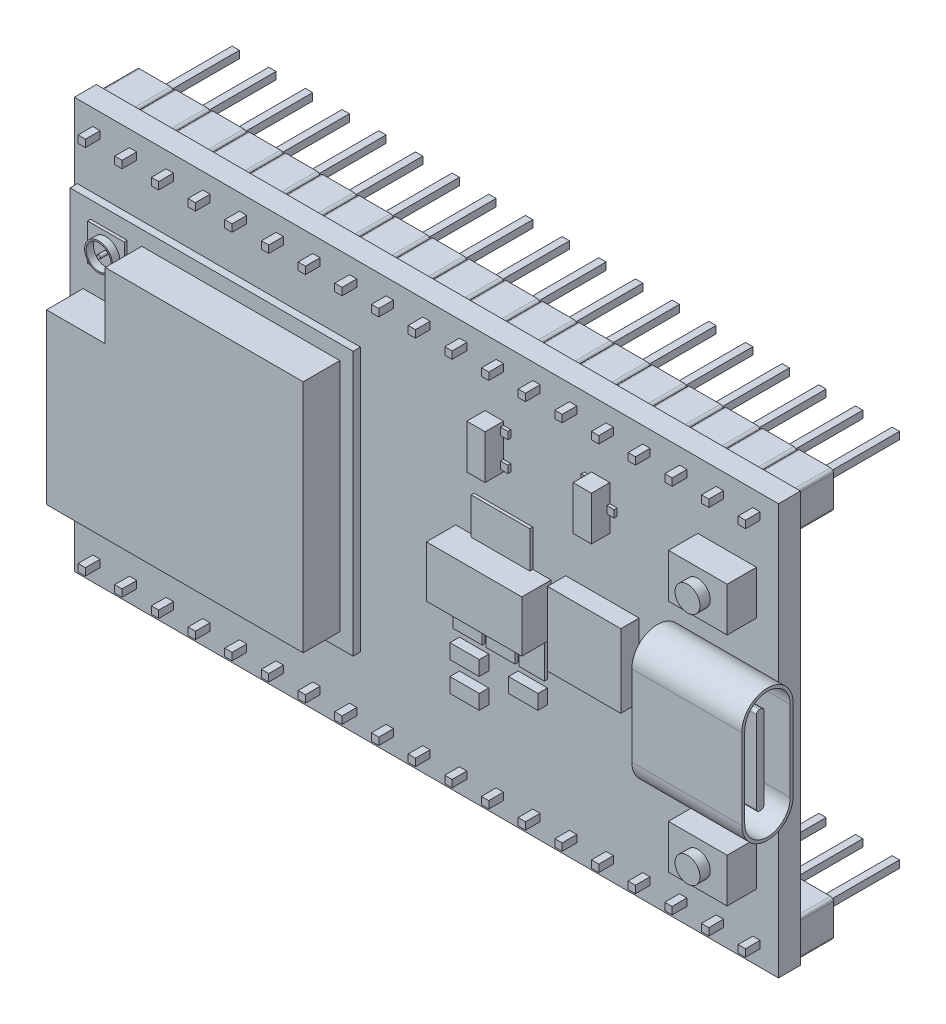
SolidWorks part; units mm, degrees
ref_plane "Front Plane" through (0, 0, 0) normal (0, 0, 1) x (1, 0, 0)
ref_plane "Top Plane" through (0, 0, 0) normal (0, 1, 0) x (1, 0, 0)
ref_plane "Right Plane" through (0, 0, 0) normal (1, 0, 0) x (0, 0, -1)
sketch "Sketch1" plane through (0, 0, 0) normal (0, 0, 1) x (1, 0, 0)
  line L1 (-24, -14) -> (24, -14)
  line L2 (-24, -14) -> (-24, 14)
  line L3 (-24, 14) -> (24, 14)
  line L4 (24, -14) -> (24, 14)
  dimension "D1" = 48
  dimension "D2" = 24
  dimension "D3" = 28
  dimension "D4" = 14
extrude "Boss-Extrude1" add sketch "Sketch1" along normal blind 1.5
sketch "Sketch2" plane through (0, 0, 0) normal (0, 0, -1) x (-1, 0, 0)
  line L1 (-23.55, -13.9) -> (-21.45, -13.9)
  line L2 (-23.75, -13.7) -> (-23.75, -11.6)
  line L3 (-23.55, -11.4) -> (-21.45, -11.4)
  line L6 (-21.05, -13.9) -> (-18.95, -13.9)
  line L8 (-21.05, -11.4) -> (-18.95, -11.4)
  line L10 (-18.55, -13.9) -> (-16.45, -13.9)
  line L12 (-18.55, -11.4) -> (-16.45, -11.4)
  line L14 (-16.05, -13.9) -> (-13.95, -13.9)
  line L16 (-16.05, -11.4) -> (-13.95, -11.4)
  line L18 (-13.55, -13.9) -> (-11.45, -13.9)
  line L20 (-13.55, -11.4) -> (-11.45, -11.4)
  line L22 (-11.05, -13.9) -> (-8.95, -13.9)
  line L24 (-11.05, -11.4) -> (-8.95, -11.4)
  line L26 (-8.55, -13.9) -> (-6.45, -13.9)
  line L28 (-8.55, -11.4) -> (-6.45, -11.4)
  line L30 (-6.05, -13.9) -> (-3.95, -13.9)
  line L32 (-6.05, -11.4) -> (-3.95, -11.4)
  line L34 (-3.55, -13.9) -> (-1.45, -13.9)
  line L36 (-3.55, -11.4) -> (-1.45, -11.4)
  line L38 (-1.05, -13.9) -> (1.05, -13.9)
  line L40 (-1.05, -11.4) -> (1.05, -11.4)
  line L42 (1.45, -13.9) -> (3.55, -13.9)
  line L44 (1.45, -11.4) -> (3.55, -11.4)
  line L46 (3.95, -13.9) -> (6.05, -13.9)
  line L48 (3.95, -11.4) -> (6.05, -11.4)
  line L50 (6.45, -13.9) -> (8.55, -13.9)
  line L52 (6.45, -11.4) -> (8.55, -11.4)
  line L54 (8.95, -13.9) -> (11.05, -13.9)
  line L56 (8.95, -11.4) -> (11.05, -11.4)
  line L58 (11.45, -13.9) -> (13.55, -13.9)
  line L60 (11.45, -11.4) -> (13.55, -11.4)
  line L62 (13.95, -13.9) -> (16.05, -13.9)
  line L64 (13.95, -11.4) -> (16.05, -11.4)
  line L66 (16.45, -13.9) -> (18.55, -13.9)
  line L68 (16.45, -11.4) -> (18.55, -11.4)
  line L70 (18.95, -13.9) -> (21.05, -13.9)
  line L72 (18.95, -11.4) -> (21.05, -11.4)
  line L74 (21.45, -13.9) -> (23.55, -13.9)
  line L75 (23.75, -13.7) -> (23.75, -11.6)
  line L76 (21.45, -11.4) -> (23.55, -11.4)
  line L78 (-24, -14) -> (-24, 14) construction
  line L79 (-1000, 0) -> (49000, 0) construction
  line L80 (21.45, 11.4) -> (23.55, 11.4)
  line L81 (23.75, 13.7) -> (23.75, 11.6)
  line L82 (21.45, 13.9) -> (23.55, 13.9)
  line L84 (18.95, 11.4) -> (21.05, 11.4)
  line L86 (18.95, 13.9) -> (21.05, 13.9)
  line L88 (16.45, 11.4) -> (18.55, 11.4)
  line L90 (16.45, 13.9) -> (18.55, 13.9)
  line L92 (13.95, 11.4) -> (16.05, 11.4)
  line L94 (13.95, 13.9) -> (16.05, 13.9)
  line L96 (11.45, 11.4) -> (13.55, 11.4)
  line L98 (11.45, 13.9) -> (13.55, 13.9)
  line L100 (8.95, 11.4) -> (11.05, 11.4)
  line L102 (8.95, 13.9) -> (11.05, 13.9)
  line L104 (6.45, 11.4) -> (8.55, 11.4)
  line L106 (6.45, 13.9) -> (8.55, 13.9)
  line L108 (3.95, 11.4) -> (6.05, 11.4)
  line L110 (3.95, 13.9) -> (6.05, 13.9)
  line L112 (1.45, 11.4) -> (3.55, 11.4)
  line L114 (1.45, 13.9) -> (3.55, 13.9)
  line L116 (-1.05, 11.4) -> (1.05, 11.4)
  line L118 (-1.05, 13.9) -> (1.05, 13.9)
  line L120 (-3.55, 11.4) -> (-1.45, 11.4)
  line L122 (-3.55, 13.9) -> (-1.45, 13.9)
  line L124 (-6.05, 11.4) -> (-3.95, 11.4)
  line L126 (-6.05, 13.9) -> (-3.95, 13.9)
  line L128 (-8.55, 11.4) -> (-6.45, 11.4)
  line L130 (-8.55, 13.9) -> (-6.45, 13.9)
  line L132 (-11.05, 11.4) -> (-8.95, 11.4)
  line L134 (-11.05, 13.9) -> (-8.95, 13.9)
  line L136 (-13.55, 11.4) -> (-11.45, 11.4)
  line L138 (-13.55, 13.9) -> (-11.45, 13.9)
  line L140 (-16.05, 11.4) -> (-13.95, 11.4)
  line L142 (-16.05, 13.9) -> (-13.95, 13.9)
  line L144 (-18.55, 11.4) -> (-16.45, 11.4)
  line L146 (-18.55, 13.9) -> (-16.45, 13.9)
  line L148 (-21.05, 11.4) -> (-18.95, 11.4)
  line L150 (-21.05, 13.9) -> (-18.95, 13.9)
  line L153 (-23.55, 11.4) -> (-21.45, 11.4)
  line L154 (-23.75, 13.7) -> (-23.75, 11.6)
  line L155 (-23.55, 13.9) -> (-21.45, 13.9)
  line L157 (21.25, -13.7) -> (21.25, -11.6) [skipped]
  line L158 (18.75, -13.7) -> (18.75, -11.6) [skipped]
  line L160 (16.25, -13.7) -> (16.25, -11.6) [skipped]
  line L163 (13.75, -13.7) -> (13.75, -11.6) [skipped]
  line L165 (11.25, -13.7) -> (11.25, -11.6) [skipped]
  line L166 (8.75, -13.7) -> (8.75, -11.6) [skipped]
  line L169 (6.25, -13.7) -> (6.25, -11.6) [skipped]
  line L171 (3.75, -13.7) -> (3.75, -11.6) [skipped]
  line L173 (1.25, -13.7) -> (1.25, -11.6) [skipped]
  line L175 (-1.25, -13.7) -> (-1.25, -11.6) [skipped]
  line L177 (-3.75, -13.7) -> (-3.75, -11.6) [skipped]
  line L179 (-6.25, -13.7) -> (-6.25, -11.6) [skipped]
  line L181 (-8.75, -13.7) -> (-8.75, -11.6) [skipped]
  line L183 (-11.25, -13.7) -> (-11.25, -11.6) [skipped]
  line L185 (-13.75, -13.7) -> (-13.75, -11.6) [skipped]
  line L187 (-16.25, -13.7) -> (-16.25, -11.6) [skipped]
  line L189 (-18.75, -13.7) -> (-18.75, -11.6) [skipped]
  line L190 (-21.25, -13.7) -> (-21.25, -11.6) [skipped]
  arc A0 (-23.55, -13.9) -> (-23.75, -13.7) centre (-23.55, -13.7) cw
  arc A1 (-21.45, -13.9) -> (-21.25, -13.7) centre (-21.45, -13.7) ccw
  arc A2 (-21.45, -11.4) -> (-21.25, -11.6) centre (-21.45, -11.6) cw
  arc A3 (-23.75, -11.6) -> (-23.55, -11.4) centre (-23.55, -11.6) cw
  arc A4 (-21.25, -11.6) -> (-21.05, -11.4) centre (-21.05, -11.6) cw
  arc A5 (-21.05, -13.9) -> (-21.25, -13.7) centre (-21.05, -13.7) cw
  arc A6 (-18.95, -13.9) -> (-18.75, -13.7) centre (-18.95, -13.7) ccw
  arc A7 (-18.95, -11.4) -> (-18.75, -11.6) centre (-18.95, -11.6) cw
  arc A8 (-18.75, -11.6) -> (-18.55, -11.4) centre (-18.55, -11.6) cw
  arc A9 (-18.55, -13.9) -> (-18.75, -13.7) centre (-18.55, -13.7) cw
  arc A10 (-16.45, -13.9) -> (-16.25, -13.7) centre (-16.45, -13.7) ccw
  arc A11 (-16.45, -11.4) -> (-16.25, -11.6) centre (-16.45, -11.6) cw
  arc A12 (-16.25, -11.6) -> (-16.05, -11.4) centre (-16.05, -11.6) cw
  arc A13 (-16.05, -13.9) -> (-16.25, -13.7) centre (-16.05, -13.7) cw
  arc A14 (-13.95, -13.9) -> (-13.75, -13.7) centre (-13.95, -13.7) ccw
  arc A15 (-13.95, -11.4) -> (-13.75, -11.6) centre (-13.95, -11.6) cw
  arc A16 (-13.75, -11.6) -> (-13.55, -11.4) centre (-13.55, -11.6) cw
  arc A17 (-13.55, -13.9) -> (-13.75, -13.7) centre (-13.55, -13.7) cw
  arc A18 (-11.45, -13.9) -> (-11.25, -13.7) centre (-11.45, -13.7) ccw
  arc A19 (-11.45, -11.4) -> (-11.25, -11.6) centre (-11.45, -11.6) cw
  arc A20 (-11.25, -11.6) -> (-11.05, -11.4) centre (-11.05, -11.6) cw
  arc A21 (-11.05, -13.9) -> (-11.25, -13.7) centre (-11.05, -13.7) cw
  arc A22 (-8.95, -13.9) -> (-8.75, -13.7) centre (-8.95, -13.7) ccw
  arc A23 (-8.95, -11.4) -> (-8.75, -11.6) centre (-8.95, -11.6) cw
  arc A24 (-8.75, -11.6) -> (-8.55, -11.4) centre (-8.55, -11.6) cw
  arc A25 (-8.55, -13.9) -> (-8.75, -13.7) centre (-8.55, -13.7) cw
  arc A26 (-6.45, -13.9) -> (-6.25, -13.7) centre (-6.45, -13.7) ccw
  arc A27 (-6.45, -11.4) -> (-6.25, -11.6) centre (-6.45, -11.6) cw
  arc A28 (-6.25, -11.6) -> (-6.05, -11.4) centre (-6.05, -11.6) cw
  arc A29 (-6.05, -13.9) -> (-6.25, -13.7) centre (-6.05, -13.7) cw
  arc A30 (-3.95, -13.9) -> (-3.75, -13.7) centre (-3.95, -13.7) ccw
  arc A31 (-3.95, -11.4) -> (-3.75, -11.6) centre (-3.95, -11.6) cw
  arc A32 (-3.75, -11.6) -> (-3.55, -11.4) centre (-3.55, -11.6) cw
  arc A33 (-3.55, -13.9) -> (-3.75, -13.7) centre (-3.55, -13.7) cw
  arc A34 (-1.45, -13.9) -> (-1.25, -13.7) centre (-1.45, -13.7) ccw
  arc A35 (-1.45, -11.4) -> (-1.25, -11.6) centre (-1.45, -11.6) cw
  arc A36 (-1.25, -11.6) -> (-1.05, -11.4) centre (-1.05, -11.6) cw
  arc A37 (-1.05, -13.9) -> (-1.25, -13.7) centre (-1.05, -13.7) cw
  arc A38 (1.05, -13.9) -> (1.25, -13.7) centre (1.05, -13.7) ccw
  arc A39 (1.05, -11.4) -> (1.25, -11.6) centre (1.05, -11.6) cw
  arc A40 (1.25, -11.6) -> (1.45, -11.4) centre (1.45, -11.6) cw
  arc A41 (1.45, -13.9) -> (1.25, -13.7) centre (1.45, -13.7) cw
  arc A42 (3.55, -13.9) -> (3.75, -13.7) centre (3.55, -13.7) ccw
  arc A43 (3.55, -11.4) -> (3.75, -11.6) centre (3.55, -11.6) cw
  arc A44 (3.75, -11.6) -> (3.95, -11.4) centre (3.95, -11.6) cw
  arc A45 (3.95, -13.9) -> (3.75, -13.7) centre (3.95, -13.7) cw
  arc A46 (6.05, -13.9) -> (6.25, -13.7) centre (6.05, -13.7) ccw
  arc A47 (6.05, -11.4) -> (6.25, -11.6) centre (6.05, -11.6) cw
  arc A48 (6.25, -11.6) -> (6.45, -11.4) centre (6.45, -11.6) cw
  arc A49 (6.45, -13.9) -> (6.25, -13.7) centre (6.45, -13.7) cw
  arc A50 (8.55, -13.9) -> (8.75, -13.7) centre (8.55, -13.7) ccw
  arc A51 (8.55, -11.4) -> (8.75, -11.6) centre (8.55, -11.6) cw
  arc A52 (8.75, -11.6) -> (8.95, -11.4) centre (8.95, -11.6) cw
  arc A53 (8.95, -13.9) -> (8.75, -13.7) centre (8.95, -13.7) cw
  arc A54 (11.05, -13.9) -> (11.25, -13.7) centre (11.05, -13.7) ccw
  arc A55 (11.05, -11.4) -> (11.25, -11.6) centre (11.05, -11.6) cw
  arc A56 (11.25, -11.6) -> (11.45, -11.4) centre (11.45, -11.6) cw
  arc A57 (11.45, -13.9) -> (11.25, -13.7) centre (11.45, -13.7) cw
  arc A58 (13.55, -13.9) -> (13.75, -13.7) centre (13.55, -13.7) ccw
  arc A59 (13.55, -11.4) -> (13.75, -11.6) centre (13.55, -11.6) cw
  arc A60 (13.75, -11.6) -> (13.95, -11.4) centre (13.95, -11.6) cw
  arc A61 (13.95, -13.9) -> (13.75, -13.7) centre (13.95, -13.7) cw
  arc A62 (16.05, -13.9) -> (16.25, -13.7) centre (16.05, -13.7) ccw
  arc A63 (16.05, -11.4) -> (16.25, -11.6) centre (16.05, -11.6) cw
  arc A64 (16.25, -11.6) -> (16.45, -11.4) centre (16.45, -11.6) cw
  arc A65 (16.45, -13.9) -> (16.25, -13.7) centre (16.45, -13.7) cw
  arc A66 (18.55, -13.9) -> (18.75, -13.7) centre (18.55, -13.7) ccw
  arc A67 (18.55, -11.4) -> (18.75, -11.6) centre (18.55, -11.6) cw
  arc A68 (18.75, -11.6) -> (18.95, -11.4) centre (18.95, -11.6) cw
  arc A69 (18.95, -13.9) -> (18.75, -13.7) centre (18.95, -13.7) cw
  arc A70 (21.05, -13.9) -> (21.25, -13.7) centre (21.05, -13.7) ccw
  arc A71 (21.05, -11.4) -> (21.25, -11.6) centre (21.05, -11.6) cw
  arc A72 (21.25, -11.6) -> (21.45, -11.4) centre (21.45, -11.6) cw
  arc A73 (21.45, -13.9) -> (21.25, -13.7) centre (21.45, -13.7) cw
  arc A74 (23.55, -13.9) -> (23.75, -13.7) centre (23.55, -13.7) ccw
  arc A75 (23.55, -11.4) -> (23.75, -11.6) centre (23.55, -11.6) cw
  arc A76 (23.55, 11.4) -> (23.75, 11.6) centre (23.55, 11.6) ccw
  arc A77 (23.55, 13.9) -> (23.75, 13.7) centre (23.55, 13.7) cw
  arc A78 (21.45, 13.9) -> (21.25, 13.7) centre (21.45, 13.7) ccw
  arc A79 (21.25, 11.6) -> (21.45, 11.4) centre (21.45, 11.6) ccw
  arc A80 (21.05, 11.4) -> (21.25, 11.6) centre (21.05, 11.6) ccw
  arc A81 (21.05, 13.9) -> (21.25, 13.7) centre (21.05, 13.7) cw
  arc A82 (18.95, 13.9) -> (18.75, 13.7) centre (18.95, 13.7) ccw
  arc A83 (18.75, 11.6) -> (18.95, 11.4) centre (18.95, 11.6) ccw
  arc A84 (18.55, 11.4) -> (18.75, 11.6) centre (18.55, 11.6) ccw
  arc A85 (18.55, 13.9) -> (18.75, 13.7) centre (18.55, 13.7) cw
  arc A86 (16.45, 13.9) -> (16.25, 13.7) centre (16.45, 13.7) ccw
  arc A87 (16.25, 11.6) -> (16.45, 11.4) centre (16.45, 11.6) ccw
  arc A88 (16.05, 11.4) -> (16.25, 11.6) centre (16.05, 11.6) ccw
  arc A89 (16.05, 13.9) -> (16.25, 13.7) centre (16.05, 13.7) cw
  arc A90 (13.95, 13.9) -> (13.75, 13.7) centre (13.95, 13.7) ccw
  arc A91 (13.75, 11.6) -> (13.95, 11.4) centre (13.95, 11.6) ccw
  arc A92 (13.55, 11.4) -> (13.75, 11.6) centre (13.55, 11.6) ccw
  arc A93 (13.55, 13.9) -> (13.75, 13.7) centre (13.55, 13.7) cw
  arc A94 (11.45, 13.9) -> (11.25, 13.7) centre (11.45, 13.7) ccw
  arc A95 (11.25, 11.6) -> (11.45, 11.4) centre (11.45, 11.6) ccw
  arc A96 (11.05, 11.4) -> (11.25, 11.6) centre (11.05, 11.6) ccw
  arc A97 (11.05, 13.9) -> (11.25, 13.7) centre (11.05, 13.7) cw
  arc A98 (8.95, 13.9) -> (8.75, 13.7) centre (8.95, 13.7) ccw
  arc A99 (8.75, 11.6) -> (8.95, 11.4) centre (8.95, 11.6) ccw
  arc A100 (8.55, 11.4) -> (8.75, 11.6) centre (8.55, 11.6) ccw
  arc A101 (8.55, 13.9) -> (8.75, 13.7) centre (8.55, 13.7) cw
  arc A102 (6.45, 13.9) -> (6.25, 13.7) centre (6.45, 13.7) ccw
  arc A103 (6.25, 11.6) -> (6.45, 11.4) centre (6.45, 11.6) ccw
  arc A104 (6.05, 11.4) -> (6.25, 11.6) centre (6.05, 11.6) ccw
  arc A105 (6.05, 13.9) -> (6.25, 13.7) centre (6.05, 13.7) cw
  arc A106 (3.95, 13.9) -> (3.75, 13.7) centre (3.95, 13.7) ccw
  arc A107 (3.75, 11.6) -> (3.95, 11.4) centre (3.95, 11.6) ccw
  arc A108 (3.55, 11.4) -> (3.75, 11.6) centre (3.55, 11.6) ccw
  arc A109 (3.55, 13.9) -> (3.75, 13.7) centre (3.55, 13.7) cw
  arc A110 (1.45, 13.9) -> (1.25, 13.7) centre (1.45, 13.7) ccw
  arc A111 (1.25, 11.6) -> (1.45, 11.4) centre (1.45, 11.6) ccw
  arc A112 (1.05, 11.4) -> (1.25, 11.6) centre (1.05, 11.6) ccw
  arc A113 (1.05, 13.9) -> (1.25, 13.7) centre (1.05, 13.7) cw
  arc A114 (-1.05, 13.9) -> (-1.25, 13.7) centre (-1.05, 13.7) ccw
  arc A115 (-1.25, 11.6) -> (-1.05, 11.4) centre (-1.05, 11.6) ccw
  arc A116 (-1.45, 11.4) -> (-1.25, 11.6) centre (-1.45, 11.6) ccw
  arc A117 (-1.45, 13.9) -> (-1.25, 13.7) centre (-1.45, 13.7) cw
  arc A118 (-3.55, 13.9) -> (-3.75, 13.7) centre (-3.55, 13.7) ccw
  arc A119 (-3.75, 11.6) -> (-3.55, 11.4) centre (-3.55, 11.6) ccw
  arc A120 (-3.95, 11.4) -> (-3.75, 11.6) centre (-3.95, 11.6) ccw
  arc A121 (-3.95, 13.9) -> (-3.75, 13.7) centre (-3.95, 13.7) cw
  arc A122 (-6.05, 13.9) -> (-6.25, 13.7) centre (-6.05, 13.7) ccw
  arc A123 (-6.25, 11.6) -> (-6.05, 11.4) centre (-6.05, 11.6) ccw
  arc A124 (-6.45, 11.4) -> (-6.25, 11.6) centre (-6.45, 11.6) ccw
  arc A125 (-6.45, 13.9) -> (-6.25, 13.7) centre (-6.45, 13.7) cw
  arc A126 (-8.55, 13.9) -> (-8.75, 13.7) centre (-8.55, 13.7) ccw
  arc A127 (-8.75, 11.6) -> (-8.55, 11.4) centre (-8.55, 11.6) ccw
  arc A128 (-8.95, 11.4) -> (-8.75, 11.6) centre (-8.95, 11.6) ccw
  arc A129 (-8.95, 13.9) -> (-8.75, 13.7) centre (-8.95, 13.7) cw
  arc A130 (-11.05, 13.9) -> (-11.25, 13.7) centre (-11.05, 13.7) ccw
  arc A131 (-11.25, 11.6) -> (-11.05, 11.4) centre (-11.05, 11.6) ccw
  arc A132 (-11.45, 11.4) -> (-11.25, 11.6) centre (-11.45, 11.6) ccw
  arc A133 (-11.45, 13.9) -> (-11.25, 13.7) centre (-11.45, 13.7) cw
  arc A134 (-13.55, 13.9) -> (-13.75, 13.7) centre (-13.55, 13.7) ccw
  arc A135 (-13.75, 11.6) -> (-13.55, 11.4) centre (-13.55, 11.6) ccw
  arc A136 (-13.95, 11.4) -> (-13.75, 11.6) centre (-13.95, 11.6) ccw
  arc A137 (-13.95, 13.9) -> (-13.75, 13.7) centre (-13.95, 13.7) cw
  arc A138 (-16.05, 13.9) -> (-16.25, 13.7) centre (-16.05, 13.7) ccw
  arc A139 (-16.25, 11.6) -> (-16.05, 11.4) centre (-16.05, 11.6) ccw
  arc A140 (-16.45, 11.4) -> (-16.25, 11.6) centre (-16.45, 11.6) ccw
  arc A141 (-16.45, 13.9) -> (-16.25, 13.7) centre (-16.45, 13.7) cw
  arc A142 (-18.55, 13.9) -> (-18.75, 13.7) centre (-18.55, 13.7) ccw
  arc A143 (-18.75, 11.6) -> (-18.55, 11.4) centre (-18.55, 11.6) ccw
  arc A144 (-18.95, 11.4) -> (-18.75, 11.6) centre (-18.95, 11.6) ccw
  arc A145 (-18.95, 13.9) -> (-18.75, 13.7) centre (-18.95, 13.7) cw
  arc A146 (-21.05, 13.9) -> (-21.25, 13.7) centre (-21.05, 13.7) ccw
  arc A147 (-21.25, 11.6) -> (-21.05, 11.4) centre (-21.05, 11.6) ccw
  arc A148 (-23.75, 11.6) -> (-23.55, 11.4) centre (-23.55, 11.6) ccw
  arc A149 (-21.45, 11.4) -> (-21.25, 11.6) centre (-21.45, 11.6) ccw
  arc A150 (-21.45, 13.9) -> (-21.25, 13.7) centre (-21.45, 13.7) cw
  arc A151 (-23.55, 13.9) -> (-23.75, 13.7) centre (-23.55, 13.7) ccw
  point P6 (-23.75, -13.9)
  point P9 (-21.25, -13.9)
  point P14 (-23.75, -11.4)
  point P430 (-23.75, 11.4)
  point P431 (-21.25, 13.9)
  point P432 (-23.75, 13.9)
  dimension "D3" = 0.2
  dimension "D1" = 2.5
  dimension "D2" = 2.5
  dimension "D5" = 0.25
  dimension "D6" = 13.9
  dimension "D4" = 19
extrude "Boss-Extrude2" add sketch "Sketch2" along normal blind 2.5
sketch "Sketch3" plane through (0, 0, -2.5) normal (0, 0, -1) x (-1, 0, 0)
  line L0 (-23.75, -11.6) -> (-23.75, -13.7) construction
  line L1 (-22.75, -12.9) -> (-22.25, -12.9)
  line L2 (-22.75, -12.9) -> (-22.75, -12.4)
  line L3 (-22.75, -12.4) -> (-22.25, -12.4)
  line L4 (-22.25, -12.9) -> (-22.25, -12.4)
  line L5 (-23.55, -13.9) -> (-21.45, -13.9) construction
  line L6 (-20.25, -12.9) -> (-20.25, -12.4)
  line L7 (-20.25, -12.9) -> (-19.75, -12.9)
  line L8 (-19.75, -12.9) -> (-19.75, -12.4)
  line L9 (-20.25, -12.4) -> (-19.75, -12.4)
  line L10 (-17.75, -12.9) -> (-17.75, -12.4)
  line L11 (-17.75, -12.9) -> (-17.25, -12.9)
  line L12 (-17.25, -12.9) -> (-17.25, -12.4)
  line L13 (-17.75, -12.4) -> (-17.25, -12.4)
  line L14 (-15.25, -12.9) -> (-15.25, -12.4)
  line L15 (-15.25, -12.9) -> (-14.75, -12.9)
  line L16 (-14.75, -12.9) -> (-14.75, -12.4)
  line L17 (-15.25, -12.4) -> (-14.75, -12.4)
  line L18 (-12.75, -12.9) -> (-12.75, -12.4)
  line L19 (-12.75, -12.9) -> (-12.25, -12.9)
  line L20 (-12.25, -12.9) -> (-12.25, -12.4)
  line L21 (-12.75, -12.4) -> (-12.25, -12.4)
  line L22 (-10.25, -12.9) -> (-10.25, -12.4)
  line L23 (-10.25, -12.9) -> (-9.75, -12.9)
  line L24 (-9.75, -12.9) -> (-9.75, -12.4)
  line L25 (-10.25, -12.4) -> (-9.75, -12.4)
  line L26 (-7.75, -12.9) -> (-7.75, -12.4)
  line L27 (-7.75, -12.9) -> (-7.25, -12.9)
  line L28 (-7.25, -12.9) -> (-7.25, -12.4)
  line L29 (-7.75, -12.4) -> (-7.25, -12.4)
  line L30 (-5.25, -12.9) -> (-5.25, -12.4)
  line L31 (-5.25, -12.9) -> (-4.75, -12.9)
  line L32 (-4.75, -12.9) -> (-4.75, -12.4)
  line L33 (-5.25, -12.4) -> (-4.75, -12.4)
  line L34 (-2.75, -12.9) -> (-2.75, -12.4)
  line L35 (-2.75, -12.9) -> (-2.25, -12.9)
  line L36 (-2.25, -12.9) -> (-2.25, -12.4)
  line L37 (-2.75, -12.4) -> (-2.25, -12.4)
  line L38 (-0.25, -12.9) -> (-0.25, -12.4)
  line L39 (-0.25, -12.9) -> (0.25, -12.9)
  line L40 (0.25, -12.9) -> (0.25, -12.4)
  line L41 (-0.25, -12.4) -> (0.25, -12.4)
  line L42 (2.25, -12.9) -> (2.25, -12.4)
  line L43 (2.25, -12.9) -> (2.75, -12.9)
  line L44 (2.75, -12.9) -> (2.75, -12.4)
  line L45 (2.25, -12.4) -> (2.75, -12.4)
  line L46 (4.75, -12.9) -> (4.75, -12.4)
  line L47 (4.75, -12.9) -> (5.25, -12.9)
  line L48 (5.25, -12.9) -> (5.25, -12.4)
  line L49 (4.75, -12.4) -> (5.25, -12.4)
  line L50 (7.25, -12.9) -> (7.25, -12.4)
  line L51 (7.25, -12.9) -> (7.75, -12.9)
  line L52 (7.75, -12.9) -> (7.75, -12.4)
  line L53 (7.25, -12.4) -> (7.75, -12.4)
  line L54 (9.75, -12.9) -> (9.75, -12.4)
  line L55 (9.75, -12.9) -> (10.25, -12.9)
  line L56 (10.25, -12.9) -> (10.25, -12.4)
  line L57 (9.75, -12.4) -> (10.25, -12.4)
  line L58 (12.25, -12.9) -> (12.25, -12.4)
  line L59 (12.25, -12.9) -> (12.75, -12.9)
  line L60 (12.75, -12.9) -> (12.75, -12.4)
  line L61 (12.25, -12.4) -> (12.75, -12.4)
  line L62 (14.75, -12.9) -> (14.75, -12.4)
  line L63 (14.75, -12.9) -> (15.25, -12.9)
  line L64 (15.25, -12.9) -> (15.25, -12.4)
  line L65 (14.75, -12.4) -> (15.25, -12.4)
  line L66 (17.25, -12.9) -> (17.25, -12.4)
  line L67 (17.25, -12.9) -> (17.75, -12.9)
  line L68 (17.75, -12.9) -> (17.75, -12.4)
  line L69 (17.25, -12.4) -> (17.75, -12.4)
  line L70 (19.75, -12.9) -> (19.75, -12.4)
  line L71 (19.75, -12.9) -> (20.25, -12.9)
  line L72 (20.25, -12.9) -> (20.25, -12.4)
  line L73 (19.75, -12.4) -> (20.25, -12.4)
  line L74 (22.25, -12.9) -> (22.25, -12.4)
  line L75 (22.25, -12.9) -> (22.75, -12.9)
  line L76 (22.75, -12.9) -> (22.75, -12.4)
  line L77 (22.25, -12.4) -> (22.75, -12.4)
  line L78 (-1000, 0) -> (49000, 0) construction
  line L79 (22.25, 12.4) -> (22.75, 12.4)
  line L80 (22.75, 12.9) -> (22.75, 12.4)
  line L81 (22.25, 12.9) -> (22.75, 12.9)
  line L82 (22.25, 12.9) -> (22.25, 12.4)
  line L83 (19.75, 12.4) -> (20.25, 12.4)
  line L84 (20.25, 12.9) -> (20.25, 12.4)
  line L85 (19.75, 12.9) -> (20.25, 12.9)
  line L86 (19.75, 12.9) -> (19.75, 12.4)
  line L87 (17.25, 12.4) -> (17.75, 12.4)
  line L88 (17.75, 12.9) -> (17.75, 12.4)
  line L89 (17.25, 12.9) -> (17.75, 12.9)
  line L90 (17.25, 12.9) -> (17.25, 12.4)
  line L91 (14.75, 12.4) -> (15.25, 12.4)
  line L92 (15.25, 12.9) -> (15.25, 12.4)
  line L93 (14.75, 12.9) -> (15.25, 12.9)
  line L94 (14.75, 12.9) -> (14.75, 12.4)
  line L95 (12.25, 12.4) -> (12.75, 12.4)
  line L96 (12.75, 12.9) -> (12.75, 12.4)
  line L97 (12.25, 12.9) -> (12.75, 12.9)
  line L98 (12.25, 12.9) -> (12.25, 12.4)
  line L99 (9.75, 12.4) -> (10.25, 12.4)
  line L100 (10.25, 12.9) -> (10.25, 12.4)
  line L101 (9.75, 12.9) -> (10.25, 12.9)
  line L102 (9.75, 12.9) -> (9.75, 12.4)
  line L103 (7.25, 12.4) -> (7.75, 12.4)
  line L104 (7.75, 12.9) -> (7.75, 12.4)
  line L105 (7.25, 12.9) -> (7.75, 12.9)
  line L106 (7.25, 12.9) -> (7.25, 12.4)
  line L107 (4.75, 12.4) -> (5.25, 12.4)
  line L108 (5.25, 12.9) -> (5.25, 12.4)
  line L109 (4.75, 12.9) -> (5.25, 12.9)
  line L110 (4.75, 12.9) -> (4.75, 12.4)
  line L111 (2.25, 12.4) -> (2.75, 12.4)
  line L112 (2.75, 12.9) -> (2.75, 12.4)
  line L113 (2.25, 12.9) -> (2.75, 12.9)
  line L114 (2.25, 12.9) -> (2.25, 12.4)
  line L115 (-0.25, 12.4) -> (0.25, 12.4)
  line L116 (0.25, 12.9) -> (0.25, 12.4)
  line L117 (-0.25, 12.9) -> (0.25, 12.9)
  line L118 (-0.25, 12.9) -> (-0.25, 12.4)
  line L119 (-2.75, 12.4) -> (-2.25, 12.4)
  line L120 (-2.25, 12.9) -> (-2.25, 12.4)
  line L121 (-2.75, 12.9) -> (-2.25, 12.9)
  line L122 (-2.75, 12.9) -> (-2.75, 12.4)
  line L123 (-5.25, 12.4) -> (-4.75, 12.4)
  line L124 (-4.75, 12.9) -> (-4.75, 12.4)
  line L125 (-5.25, 12.9) -> (-4.75, 12.9)
  line L126 (-5.25, 12.9) -> (-5.25, 12.4)
  line L127 (-7.75, 12.4) -> (-7.25, 12.4)
  line L128 (-7.25, 12.9) -> (-7.25, 12.4)
  line L129 (-7.75, 12.9) -> (-7.25, 12.9)
  line L130 (-7.75, 12.9) -> (-7.75, 12.4)
  line L131 (-10.25, 12.4) -> (-9.75, 12.4)
  line L132 (-9.75, 12.9) -> (-9.75, 12.4)
  line L133 (-10.25, 12.9) -> (-9.75, 12.9)
  line L134 (-10.25, 12.9) -> (-10.25, 12.4)
  line L135 (-12.75, 12.4) -> (-12.25, 12.4)
  line L136 (-12.25, 12.9) -> (-12.25, 12.4)
  line L137 (-12.75, 12.9) -> (-12.25, 12.9)
  line L138 (-12.75, 12.9) -> (-12.75, 12.4)
  line L139 (-15.25, 12.4) -> (-14.75, 12.4)
  line L140 (-14.75, 12.9) -> (-14.75, 12.4)
  line L141 (-15.25, 12.9) -> (-14.75, 12.9)
  line L142 (-15.25, 12.9) -> (-15.25, 12.4)
  line L143 (-17.75, 12.4) -> (-17.25, 12.4)
  line L144 (-17.25, 12.9) -> (-17.25, 12.4)
  line L145 (-17.75, 12.9) -> (-17.25, 12.9)
  line L146 (-17.75, 12.9) -> (-17.75, 12.4)
  line L147 (-20.25, 12.4) -> (-19.75, 12.4)
  line L148 (-19.75, 12.9) -> (-19.75, 12.4)
  line L149 (-20.25, 12.9) -> (-19.75, 12.9)
  line L150 (-20.25, 12.9) -> (-20.25, 12.4)
  line L151 (-22.25, 12.9) -> (-22.25, 12.4)
  line L152 (-22.75, 12.4) -> (-22.25, 12.4)
  line L153 (-22.75, 12.9) -> (-22.75, 12.4)
  line L154 (-22.75, 12.9) -> (-22.25, 12.9)
  point P6 (-23.75, -12.65)
  dimension "D1" = 0.5
  dimension "D2" = 0.5
  dimension "D3" = 1
  dimension "D4" = 1
  dimension "D5" = 19
extrude "Boss-Extrude3" add sketch "Sketch3" along normal blind 5.5 and the other way blind 5
sketch "Sketch4" plane through (24, 0, 0) normal (1, 0, 0) x (0, 0, -1)
  line L0 (-3.25, -2.75) -> (-3.25, 2.75) construction
  line L1 (-5, -2.75) -> (-5, 2.75)
  line L2 (-1.5, -2.75) -> (-1.5, 2.75)
  line L3 (-1.5, -14) -> (-1.5, 14) construction
  line L4 (-4.8, -2.75) -> (-4.8, 2.75)
  line L5 (-1.7, -2.75) -> (-1.7, 2.75)
  arc A0 (-5, -2.75) -> (-1.5, -2.75) centre (-3.25, -2.75) ccw
  arc A1 (-1.5, 2.75) -> (-5, 2.75) centre (-3.25, 2.75) ccw
  arc A2 (-1.7, 2.75) -> (-4.8, 2.75) centre (-3.25, 2.75) ccw
  arc A3 (-4.8, -2.75) -> (-1.7, -2.75) centre (-3.25, -2.75) ccw
  point P2 (-3.25, 0)
  dimension "D1" = 9
  dimension "D2" = 3.5
  dimension "D3" = 2.75
  dimension "D4" = 0.2
extrude "Boss-Extrude4" add sketch "Sketch4" along normal blind 7 from offset 6 offset against normal yes
sketch "Sketch5" plane through (18, 0, 0) normal (-1, 0, 0) x (0, 0, 1)
  line L2 (5, -2.75) -> (5, 2.75)
  line L3 (1.5, 2.75) -> (1.5, -2.75)
  line L4 (5, -2.75) -> (5, 2.75)
  line L5 (1.5, 2.75) -> (1.5, -2.75)
  arc A2 (1.5, -2.75) -> (5, -2.75) centre (3.25, -2.75) ccw
  arc A3 (5, 2.75) -> (1.5, 2.75) centre (3.25, 2.75) ccw
  arc A4 (1.5, -2.75) -> (5, -2.75) centre (3.25, -2.75) ccw
  arc A5 (5, 2.75) -> (1.5, 2.75) centre (3.25, 2.75) ccw
  dimension "D1" = 0
extrude "Boss-Extrude5" add sketch "Sketch5" along normal blind 0.5
sketch "Sketch6" plane through (18, 0, 0) normal (1, 0, 0) x (0, 0, -1)
  line L0 (-1.7, -2.75) -> (-1.7, 2.75) construction
  line L1 (-3.3, -3) -> (-3.2, -3)
  line L2 (-3.5, -2.8) -> (-3.5, 2.8)
  line L3 (-3.3, 3) -> (-3.2, 3)
  line L4 (-3, -2.8) -> (-3, 2.8)
  arc A0 (-3.3, -3) -> (-3.5, -2.8) centre (-3.3, -2.8) cw
  arc A1 (-3.2, -3) -> (-3, -2.8) centre (-3.2, -2.8) ccw
  arc A2 (-3.2, 3) -> (-3, 2.8) centre (-3.2, 2.8) cw
  arc A3 (-3.5, 2.8) -> (-3.3, 3) centre (-3.3, 2.8) cw
  point P6 (-3.5, -3)
  point P11 (-3, 3)
  point P14 (-3.5, 3)
  dimension "D3" = 0.2
  dimension "D1" = 6
  dimension "D2" = 0.5
  dimension "D4" = 3
  dimension "D5" = 1.3
extrude "Boss-Extrude6" add sketch "Sketch6" along normal blind 6.5
sketch "Sketch7" plane through (0, 0, 1.5) normal (0, 0, 1) x (1, 0, 0)
  line L0 (-24, 14) -> (-24, -14) construction
  line L1 (-23.8, -9) -> (-4.5, -9)
  line L2 (-23.8, -9) -> (-23.8, 9)
  line L3 (-23.8, 9) -> (-4.5, 9)
  line L4 (-4.5, -9) -> (-4.5, 9)
  dimension "D1" = 19.3
  dimension "D2" = 0.2
  dimension "D3" = 18
  dimension "D4" = 9
extrude "Boss-Extrude7" add sketch "Sketch7" along normal blind 0.5
sketch "Sketch8" plane through (0, 0, 2) normal (0, 0, 1) x (1, 0, 0)
  line L0 (-4.5, -9) -> (-4.5, 9) construction
  line L1 (-22.9, -8) -> (-5.4, -8)
  line L2 (-22.9, -8) -> (-22.9, 8)
  line L3 (-22.9, 8) -> (-5.4, 8)
  line L4 (-5.4, -8) -> (-5.4, 8)
  line L6 (-22.9, 8) -> (-18.9, 8)
  line L7 (-22.9, 8) -> (-22.9, 3.5)
  line L8 (-22.9, 3.5) -> (-18.9, 3.5)
  line L9 (-18.9, 8) -> (-18.9, 3.5)
  dimension "D1" = 17.5
  dimension "D2" = 16
  dimension "D3" = 8
  dimension "D4" = 0.9
  dimension "D5" = 4.5
  dimension "D6" = 4
extrude "Boss-Extrude8" add sketch "Sketch8" along normal blind 2.5 contours L3 L9 L8 L2 L1 L4 region at (-13.6863, -0.395, 2)
sketch "Sketch9" plane through (0, 0, 2) normal (0, 0, 1) x (1, 0, 0)
  line L0 (-18.9, 8) -> (-5.4, 8) construction
  line L1 (-22.4, 5.35) -> (-19.9, 5.35)
  line L2 (-22.4, 5.35) -> (-22.4, 7.85)
  line L3 (-22.4, 7.85) -> (-19.9, 7.85)
  line L4 (-19.9, 5.35) -> (-19.9, 7.85)
  line L5 (-22.9, -8) -> (-22.9, 3.5) construction
  dimension "D1" = 2.5
  dimension "D2" = 2.5
  dimension "D3" = 0.15
  dimension "D4" = 0.5
extrude "Boss-Extrude9" add sketch "Sketch9" along normal blind 0.2
sketch "Sketch10" plane through (0, 0, 2.2) normal (0, 0, 1) x (1, 0, 0)
  line L1 (-22.4, 7.85) -> (-22.4, 5.35) construction
  line L2 (-22.4, 5.35) -> (-19.9, 5.35) construction
  circle A0 centre (-21.15, 6.6) radius 0.95
  circle A1 centre (-21.15, 6.6) radius 0.85
  circle A2 centre (-21.15, 6.6) radius 0.125
  dimension "D1" = 1.9
  dimension "D5" = 0.25
  dimension "D2" = 1.25
  dimension "D3" = 1.25
  dimension "D4" = 0.1
extrude "Boss-Extrude10" add sketch "Sketch10" along normal blind 0.5 contours A0 A1 | A2 region at (-22.0731, 6.6, 2.2) region at (-21.15, 6.6, 2.2)
sketch "Sketch11" plane through (0, 0, 1.5) normal (0, 0, 1) x (1, 0, 0)
  line L0 (17.5, -2.75) -> (17.5, 2.75) construction
  line L1 (9.5, -2.5) -> (14.5, -2.5)
  line L2 (9.5, -2.5) -> (9.5, 2.5)
  line L3 (9.5, 2.5) -> (14.5, 2.5)
  line L4 (14.5, -2.5) -> (14.5, 2.5)
  line L6 (11.25, 6.5) -> (12.5, 6.5)
  line L7 (11.25, 6.5) -> (11.25, 9.5)
  line L8 (11.25, 9.5) -> (12.5, 9.5)
  line L9 (12.5, 6.5) -> (12.5, 9.5)
  line L10 (4, 6.5) -> (5.25, 6.5)
  line L11 (4, 6.5) -> (4, 9.5)
  line L12 (4, 9.5) -> (5.25, 9.5)
  line L13 (5.25, 6.5) -> (5.25, 9.5)
  dimension "D1" = 5
  dimension "D2" = 3
  dimension "D3" = 2.5
  dimension "D4" = 1.25
  dimension "D5" = 1.25
  dimension "D6" = 3
  dimension "D7" = 3
  dimension "D8" = 4
  dimension "D9" = 6
  dimension "D10" = 3
extrude "Boss-Extrude11" add sketch "Sketch11" along normal blind 1.25
sketch "Sketch12" plane through (0, 0, 1.5) normal (0, 0, 1) x (1, 0, 0)
  line L0 (9.5, 2.5) -> (9.5, -2.5) construction
  line L1 (2, -1.75) -> (8.5, -1.75)
  line L2 (2, -1.75) -> (2, 1.75)
  line L3 (2, 1.75) -> (8.5, 1.75)
  line L4 (8.5, -1.75) -> (8.5, 1.75)
  point P7 (9.5, 0)
  dimension "D1" = 6.5
  dimension "D2" = 3.5
  dimension "D3" = 1.75
  dimension "D4" = 1
extrude "Boss-Extrude12" add sketch "Sketch12" along normal blind 2
sketch "Sketch13" plane through (0, 0, 1.5) normal (0, 0, 1) x (1, 0, 0)
  line L0 (4, 9.5) -> (4, 6.5) construction
  line L1 (4, 7.75) -> (3.5, 7.75)
  line L2 (4, 7.75) -> (4, 8.25)
  line L3 (4, 8.25) -> (3.5, 8.25)
  line L4 (3.5, 7.75) -> (3.5, 8.25)
  line L6 (4, 6.5) -> (5.25, 6.5) construction
  line L7 (5.25, 6.5) -> (5.25, 9.5) construction
  line L8 (5.25, 8.75) -> (5.75, 8.75)
  line L9 (5.25, 8.75) -> (5.25, 9.25)
  line L10 (5.25, 9.25) -> (5.75, 9.25)
  line L11 (5.75, 8.75) -> (5.75, 9.25)
  line L12 (5.25, 9.5) -> (4, 9.5) construction
  line L13 (5.25, 7.25) -> (5.75, 7.25)
  line L14 (5.25, 7.25) -> (5.25, 6.75)
  line L15 (5.25, 6.75) -> (5.75, 6.75)
  line L16 (5.75, 7.25) -> (5.75, 6.75)
  line L17 (4, 6.5) -> (5.25, 6.5) construction
  line L18 (8.25, -992.2125) -> (8.25, 49007.7875) construction
  line L19 (5.25, 6.5) -> (11.25, 6.5)
  line L20 (10.75, 7.25) -> (10.75, 6.75)
  line L21 (11.25, 6.75) -> (10.75, 6.75)
  line L22 (11.25, 7.25) -> (11.25, 6.75)
  line L23 (11.25, 7.25) -> (10.75, 7.25)
  line L24 (10.75, 8.75) -> (10.75, 9.25)
  line L25 (11.25, 9.25) -> (10.75, 9.25)
  line L26 (11.25, 8.75) -> (11.25, 9.25)
  line L27 (11.25, 8.75) -> (10.75, 8.75)
  line L28 (13, 7.75) -> (13, 8.25)
  line L29 (12.5, 8.25) -> (13, 8.25)
  line L30 (12.5, 7.75) -> (12.5, 8.25)
  line L31 (12.5, 7.75) -> (13, 7.75)
  line L32 (2, -1.75) -> (8.5, -1.75) construction
  line L33 (2, -1.75) -> (4, -1.75)
  line L34 (2, -1.75) -> (2, -4.25)
  line L35 (2, -4.25) -> (4, -4.25)
  line L36 (4, -1.75) -> (4, -4.25)
  line L37 (8.5, -1.75) -> (6.5, -1.75)
  line L38 (8.5, -1.75) -> (8.5, -4.25)
  line L39 (8.5, -4.25) -> (6.5, -4.25)
  line L40 (6.5, -1.75) -> (6.5, -4.25)
  line L41 (4.25, -1.75) -> (6.25, -1.75)
  line L42 (4.25, -1.75) -> (4.25, -4.25)
  line L43 (4.25, -4.25) -> (6.25, -4.25)
  line L44 (6.25, -1.75) -> (6.25, -4.25)
  line L45 (8.5, 1.75) -> (2, 1.75) construction
  line L46 (3.25, 1.75) -> (7.25, 1.75)
  line L47 (3.25, 1.75) -> (3.25, 4.25)
  line L48 (3.25, 4.25) -> (7.25, 4.25)
  line L49 (7.25, 1.75) -> (7.25, 4.25)
  line L50 (2, 1.75) -> (2, -1.75) construction
  dimension "D1" = 0.5
  dimension "D2" = 0.5
  dimension "D3" = 1.25
  dimension "D4" = 0.5
  dimension "D5" = 0.25
  dimension "D6" = 0.25
  dimension "D7" = 0.5
  dimension "D8" = 0.5
  dimension "D9" = 3
  dimension "D10" = 2
  dimension "D11" = 2
  dimension "D12" = 2
  dimension "D13" = 0.25
  dimension "D14" = 2.5
  dimension "D15" = 4
  dimension "D16" = 2.5
  dimension "D17" = 1.25
extrude "Boss-Extrude13" add sketch "Sketch13" along normal blind 0.2 contours L36 L33 L34 L35 | L44 L41 L42 L43 | L39 L18 L37 L40 | L46 L49 L48 L47 | L16 L13 L14 L15 | L8 L11 L10 L9 | L4 L1 L2 L3 | L27 L26 L25 L24 | L22 L23 L20 L21 | L30 L31 L28 L29 region at (3.75, 8, 1.5) region at (5.5, 9, 1.5) region at (5.5, 7, 1.5) region at (7.375, -3, 1.5) region at (11, 7, 1.5) region at (11, 9, 1.5) region at (12.75, 8, 1.5) region at (3, -3, 1.5) region at (5.25, -3, 1.5) region at (5.25, 3, 1.5)
sketch "Sketch14" plane through (0, 0, 1.5) normal (0, 0, 1) x (1, 0, 0)
  line L0 (2, 1.75) -> (2, -4.25) construction
  line L1 (2.25, -4.75) -> (4.25, -4.75)
  line L2 (2.25, -4.75) -> (2.25, -5.75)
  line L3 (2.25, -5.75) -> (4.25, -5.75)
  line L4 (4.25, -4.75) -> (4.25, -5.75)
  line L5 (6.25, -4.75) -> (8.25, -4.75)
  line L6 (6.25, -4.75) -> (6.25, -5.75)
  line L7 (6.25, -5.75) -> (8.25, -5.75)
  line L8 (8.25, -4.75) -> (8.25, -5.75)
  line L9 (2.25, -6.75) -> (4.25, -6.75)
  line L10 (2.25, -6.75) -> (2.25, -7.75)
  line L11 (2.25, -7.75) -> (4.25, -7.75)
  line L12 (4.25, -6.75) -> (4.25, -7.75)
  line L13 (2, -4.25) -> (4, -4.25) construction
  point P12 (3.25, -5.75)
  point P13 (2.25, -5.25)
  point P16 (3.25, -4.75)
  dimension "D1" = 1
  dimension "D2" = 1
  dimension "D3" = 1
  dimension "D4" = 2
  dimension "D5" = 1
  dimension "D6" = 2
  dimension "D7" = 2
  dimension "D8" = 0.25
  dimension "D9" = 0.5
  dimension "D10" = 2
extrude "Boss-Extrude14" add sketch "Sketch14" along normal blind 0.65
sketch "Sketch15" plane through (0, 0, 1.5) normal (0, 0, 1) x (1, 0, 0)
  line L0 (17.5, -4.5) -> (25, -4.5) construction
  line L1 (18.5, 6.5) -> (22.5, 6.5)
  line L2 (18.5, 6.5) -> (18.5, 9.5)
  line L3 (18.5, 9.5) -> (22.5, 9.5)
  line L4 (22.5, 6.5) -> (22.5, 9.5)
  line L5 (18.5, -9.5) -> (22.5, -9.5)
  line L6 (18.5, -9.5) -> (18.5, -6.5)
  line L7 (18.5, -6.5) -> (22.5, -6.5)
  line L8 (22.5, -9.5) -> (22.5, -6.5)
  line L9 (25, 4.5) -> (17.5, 4.5) construction
  line L10 (24, 2.75) -> (24, 14) construction
  line L11 (24, -14) -> (24, -2.75) construction
  dimension "D1" = 4
  dimension "D2" = 4
  dimension "D3" = 3
  dimension "D4" = 3
  dimension "D5" = 2
  dimension "D6" = 2
  dimension "D7" = 1.5
  dimension "D8" = 1.5
extrude "Boss-Extrude15" add sketch "Sketch15" along normal blind 2
sketch "Sketch16" plane through (0, 0, 3.5) normal (0, 0, 1) x (1, 0, 0)
  line L0 (22.5, 6.5) -> (22.5, 9.5) construction
  line L1 (18.5, 6.5) -> (22.5, 6.5) construction
  line L2 (22.5, -9.5) -> (22.5, -6.5) construction
  line L3 (18.5, -9.5) -> (22.5, -9.5) construction
  circle A0 centre (20.5, 8) radius 0.85
  circle A1 centre (20.5, -8) radius 0.85
  dimension "D1" = 1.7
  dimension "D2" = 1.7
  dimension "D3" = 2
  dimension "D4" = 1.5
  dimension "D5" = 2
  dimension "D6" = 1.5
extrude "Boss-Extrude16" add sketch "Sketch16" along normal blind 0.7
